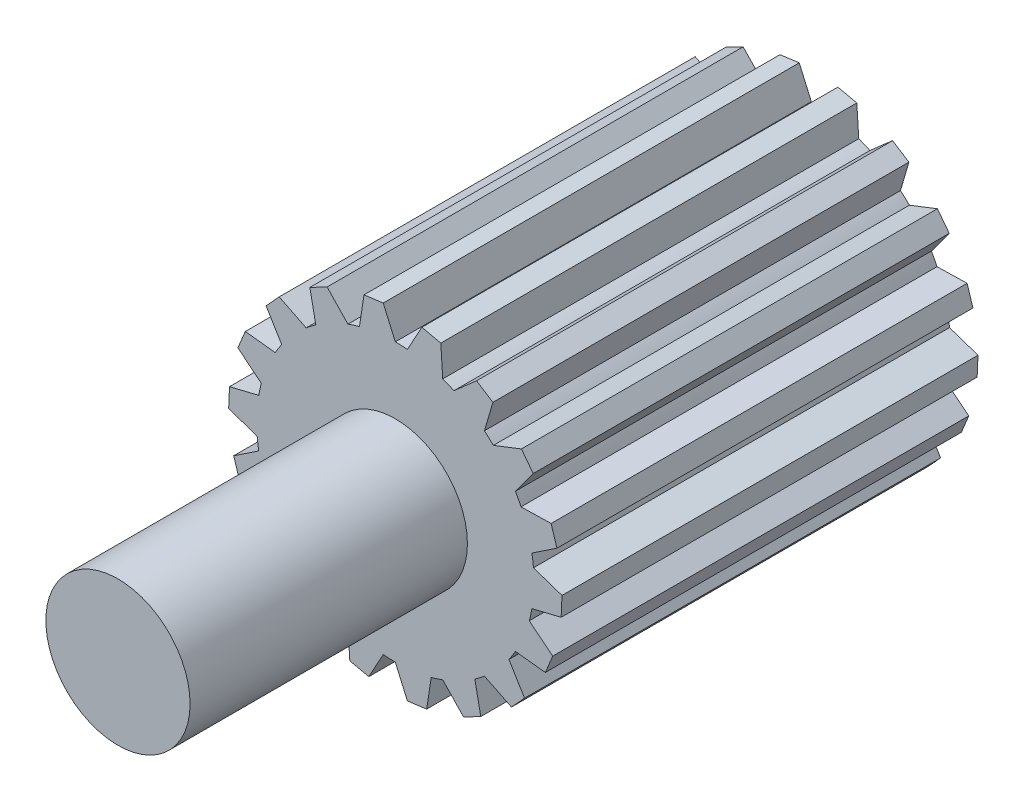
SolidWorks part; units mm, degrees
ref_plane "Front Plane" through (0, 0, 0) normal (0, 0, 1) x (1, 0, 0)
ref_plane "Top Plane" through (0, 0, 0) normal (0, 1, 0) x (1, 0, 0)
ref_plane "Right Plane" through (0, 0, 0) normal (1, 0, 0) x (0, 0, -1)
sketch "Sketch1" plane through (0, 0, 0) normal (0, 0, 1) x (1, 0, 0)
  circle A0 centre (0, 0) radius 5
  circle A1 centre (0, 0) radius 2.6
extrude "Boss-Extrude1" add sketch "Sketch1" along normal blind 15 contours A0
extrude "Boss-Extrude2" add sketch "Sketch1<3>" along normal blind 25 contours A1
sketch "Sketch1<3>" plane through (0, 0, 0) normal (0, 0, 1) x (1, 0, 0) same geometry as "Sketch1"
sketch "Sketch2" plane through (0, 0, 0) normal (0, 0, -1) x (-1, 0, 0)
  line L0 (0, 0) -> (0, 5) construction
  line L1 (0, 0) -> (1.2941, 4.8296) construction
  line L2 (0, 0) -> (0.7832, 5.9487) construction
  line L3 (0.4362, 5.9944) -> (1.1302, 5.903)
  line L4 (1.1302, 5.903) -> (1.2941, 4.8296)
  line L5 (0.4362, 5.9944) -> (0, 5)
  line L6 (2.46, 5.4837) -> (3.0809, 5.1605)
  line L7 (3.0809, 5.1605) -> (2.8679, 4.0958)
  line L8 (2.46, 5.4837) -> (1.7101, 4.6985)
  line L9 (4.1872, 4.3116) -> (4.6601, 3.7955)
  line L10 (4.6601, 3.7955) -> (4.0958, 2.8679)
  line L11 (4.1872, 4.3116) -> (3.2139, 3.8302)
  line L12 (5.4093, 2.6195) -> (5.6772, 1.9727)
  line L13 (5.6772, 1.9727) -> (4.8296, 1.2941)
  line L14 (5.4093, 2.6195) -> (4.3301, 2.5)
  line L15 (5.979, 0.6114) -> (6.0096, -0.088)
  line L16 (6.0096, -0.088) -> (4.981, -0.4358)
  line L17 (5.979, 0.6114) -> (4.924, 0.8682)
  line L18 (5.8275, -1.4704) -> (5.6171, -2.138)
  line L19 (5.6171, -2.138) -> (4.5315, -2.1131)
  line L20 (5.8275, -1.4704) -> (4.924, -0.8682)
  line L21 (4.9732, -3.3749) -> (4.5471, -3.9302)
  line L22 (4.5471, -3.9302) -> (3.5355, -3.5355)
  line L23 (4.9732, -3.3749) -> (4.3301, -2.5)
  line L24 (3.519, -4.8723) -> (2.9286, -5.2484)
  line L25 (2.9286, -5.2484) -> (2.1131, -4.5315)
  line L26 (3.519, -4.8723) -> (3.2139, -3.8302)
  line L27 (1.6403, -5.782) -> (0.9569, -5.9335)
  line L28 (0.9569, -5.9335) -> (0.4358, -4.981)
  line L29 (1.6403, -5.782) -> (1.7101, -4.6985)
  line L30 (-0.4362, -5.9944) -> (-1.1302, -5.903)
  line L31 (-1.1302, -5.903) -> (-1.2941, -4.8296)
  line L32 (-0.4362, -5.9944) -> (0, -5)
  line L33 (-2.46, -5.4837) -> (-3.0809, -5.1605)
  line L34 (-3.0809, -5.1605) -> (-2.8679, -4.0958)
  line L35 (-2.46, -5.4837) -> (-1.7101, -4.6985)
  line L36 (-4.1872, -4.3116) -> (-4.6601, -3.7955)
  line L37 (-4.6601, -3.7955) -> (-4.0958, -2.8679)
  line L38 (-4.1872, -4.3116) -> (-3.2139, -3.8302)
  line L39 (-5.4093, -2.6195) -> (-5.6772, -1.9727)
  line L40 (-5.6772, -1.9727) -> (-4.8296, -1.2941)
  line L41 (-5.4093, -2.6195) -> (-4.3301, -2.5)
  line L42 (-5.979, -0.6114) -> (-6.0096, 0.088)
  line L43 (-6.0096, 0.088) -> (-4.981, 0.4358)
  line L44 (-5.979, -0.6114) -> (-4.924, -0.8682)
  line L45 (-5.8275, 1.4704) -> (-5.6171, 2.138)
  line L46 (-5.6171, 2.138) -> (-4.5315, 2.1131)
  line L47 (-5.8275, 1.4704) -> (-4.924, 0.8682)
  line L48 (-4.9732, 3.3749) -> (-4.5471, 3.9302)
  line L49 (-4.5471, 3.9302) -> (-3.5355, 3.5355)
  line L50 (-4.9732, 3.3749) -> (-4.3301, 2.5)
  line L51 (-3.519, 4.8723) -> (-2.9286, 5.2484)
  line L52 (-2.9286, 5.2484) -> (-2.1131, 4.5315)
  line L53 (-3.519, 4.8723) -> (-3.2139, 3.8302)
  line L54 (-1.6403, 5.782) -> (-0.9569, 5.9335)
  line L55 (-0.9569, 5.9335) -> (-0.4358, 4.981)
  line L56 (-1.6403, 5.782) -> (-1.7101, 4.6985)
  circle A0 centre (0, 0) radius 5 construction
  arc A1 (1.2941, 4.8296) -> (0, 5) centre (0, 0) ccw
  arc A2 (2.8679, 4.0958) -> (1.7101, 4.6985) centre (0, 0) ccw
  arc A3 (4.0958, 2.8679) -> (3.2139, 3.8302) centre (0, 0) ccw
  arc A4 (4.8296, 1.2941) -> (4.3301, 2.5) centre (0, 0) ccw
  arc A5 (4.981, -0.4358) -> (4.924, 0.8682) centre (0, 0) ccw
  arc A6 (4.5315, -2.1131) -> (4.924, -0.8682) centre (0, 0) ccw
  arc A7 (3.5355, -3.5355) -> (4.3301, -2.5) centre (0, 0) ccw
  arc A8 (2.1131, -4.5315) -> (3.2139, -3.8302) centre (0, 0) ccw
  arc A9 (0.4358, -4.981) -> (1.7101, -4.6985) centre (0, 0) ccw
  arc A10 (-1.2941, -4.8296) -> (0, -5) centre (0, 0) ccw
  arc A11 (-2.8679, -4.0958) -> (-1.7101, -4.6985) centre (0, 0) ccw
  arc A12 (-4.0958, -2.8679) -> (-3.2139, -3.8302) centre (0, 0) ccw
  arc A13 (-4.8296, -1.2941) -> (-4.3301, -2.5) centre (0, 0) ccw
  arc A14 (-4.981, 0.4358) -> (-4.924, -0.8682) centre (0, 0) ccw
  arc A15 (-4.5315, 2.1131) -> (-4.924, 0.8682) centre (0, 0) ccw
  arc A16 (-3.5355, 3.5355) -> (-4.3301, 2.5) centre (0, 0) ccw
  arc A17 (-2.1131, 4.5315) -> (-3.2139, 3.8302) centre (0, 0) ccw
  arc A18 (-0.4358, 4.981) -> (-1.7101, 4.6985) centre (0, 0) ccw
  point P11 (0.7832, 5.9487)
  point P20 (2.7705, 5.3221)
  point P26 (4.4237, 4.0535)
  point P32 (5.5433, 2.2961)
  point P38 (5.9943, 0.2617)
  point P44 (5.7223, -1.8042)
  point P50 (4.7601, -3.6526)
  point P56 (3.2238, -5.0603)
  point P62 (1.2986, -5.8578)
  point P68 (-0.7832, -5.9487)
  point P74 (-2.7705, -5.3221)
  point P80 (-4.4237, -4.0535)
  point P86 (-5.5433, -2.2961)
  point P92 (-5.9943, -0.2617)
  point P98 (-5.7223, 1.8042)
  point P104 (-4.7601, 3.6526)
  point P110 (-3.2238, 5.0603)
  point P116 (-1.2986, 5.8578)
  point P117 (0, 0)
  dimension "D1" = 18
extrude "Boss-Extrude3" add sketch "Sketch2" against normal blind 15
